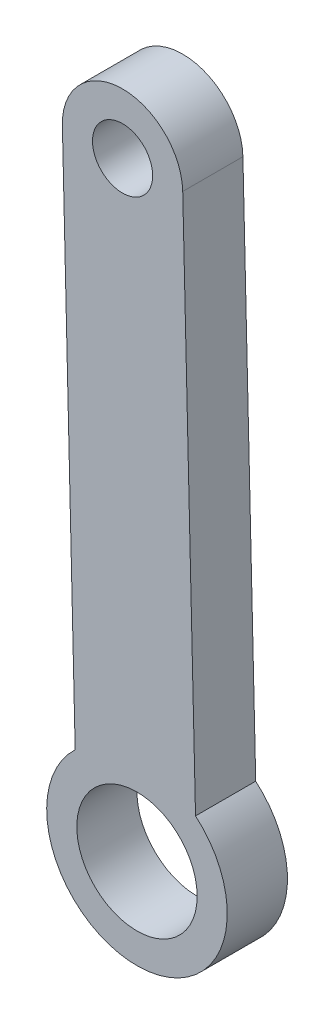
SolidWorks part; units mm, degrees
ref_plane "Front Plane" through (0, 0, 0) normal (0, 0, 1) x (1, 0, 0)
ref_plane "Top Plane" through (0, 0, 0) normal (0, 1, 0) x (1, 0, 0)
ref_plane "Right Plane" through (0, 0, 0) normal (1, 0, 0) x (0, 0, -1)
sketch "Sketch1" plane through (0, 0, 0) normal (0, 0, 1) x (0.9997, 0.0239, 0)
  line L0 (10.01, -0.02) -> (5.01, -0.02) construction
  line L1 (10.01, 49.98) -> (0.01, 49.98) construction
  line L2 (10.01, 49.98) -> (10.01, -0.02)
  line L3 (10.01, -0.02) -> (0.01, -0.02) construction
  line L4 (0.01, 49.98) -> (0.01, -0.02)
  line L6 (10.01, 24.98) -> (0.01, 24.98) construction
  circle A1 centre (5.01, 49.98) radius 2.5
  arc A2 (0.01, -0.02) -> (10.01, -0.02) centre (5.01, -0.02) ccw
  arc A3 (10.01, 49.98) -> (0.01, 49.98) centre (5.01, 49.98) ccw
  circle A4 centre (5.01, -0.02) radius 7.5
  circle A5 centre (5.01, -0.02) radius 5
  dimension "D1" = 5
  dimension "D4" = 15
  dimension "D6" = 10
  dimension "D2" = 50
  dimension "D3" = 10
  dimension "D5" = 50
extrude "Boss-Extrude1" add sketch "Sketch1" along normal blind 5 contours L6 L2 L1 L4 A1 | L2 L6 L4 L3 A5 L0 | A4 | A5 region at (4.3013, 29.6619, 0) region at (4.8833, 5.3544, 0)
move or copy body "Body-Move/Copy1" [suppressed] bodies to move or copy 101
